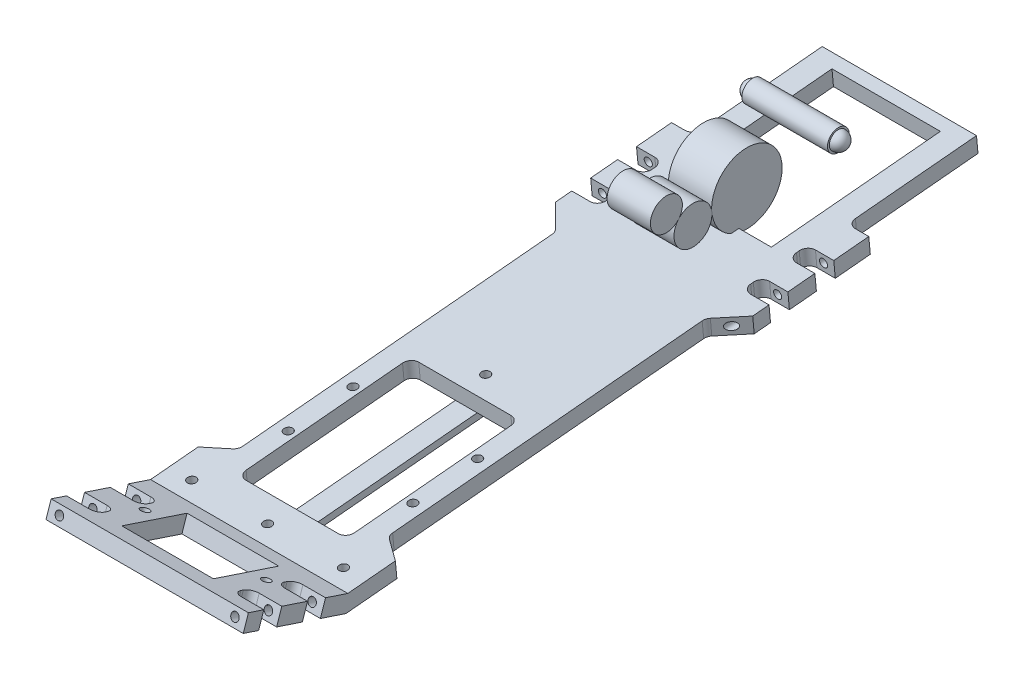
SolidWorks part; units mm, degrees
ref_plane "Front Plane" through (0, 0, 0) normal (0, 0, 1) x (1, 0, 0)
ref_plane "Top Plane" through (0, 0, 0) normal (0, 1, 0) x (1, 0, 0)
ref_plane "Right Plane" through (0, 0, 0) normal (1, 0, 0) x (0, 0, -1)
sketch "Sketch39" plane through (0, 0, 0) normal (1, 0, 0) x (0, 0, -1)
  line L6 (-42.1967, -24.4297) -> (-64.4913, -26.5105)
  line L7 (198.4523, -1.9694) -> (199.1598, -9.55)
  line L8 (-46.4598, -32.3618) -> (199.1598, -9.55)
  line L9 (-46.4598, -32.3618) -> (-111.0949, -11.0354)
  line L10 (-111.0949, -11.0354) -> (-113.4962, -18.2671)
  line L11 (-113.4962, -18.2671) -> (-65.3752, -34.2461)
sketch "Sketch2" plane through (0, 0, 0) normal (1, 0, 0) x (0, 0, -1)
  line L0 (-113.4962, -18.2671) -> (-65.3752, -34.2461)
  line L1 (-65.3752, -34.2461) -> (240.9571, -5.6556)
  line L2 (-64.4913, -26.5105) -> (240.249, 1.9315)
  line L3 (-111.0949, -11.0354) -> (-64.4913, -26.5105)
  line L4 (-113.4962, -18.2671) -> (-111.0949, -11.0354)
  line L6 (240.249, 1.9315) -> (240.9571, -5.6556)
  dimension "D1" = 156.299
  dimension "D2" = 7.62
  dimension "D3" = 7.62
extrude "Frame" add sketch "Sketch2" along normal mid plane 92.456 separate body
sketch "Sketch7" plane through (0, -20.3145, -1.896) normal (0, 0.9957, 0.0929) x (1, 0, 0)
  line L0 (0, -61.0081) -> (0, 34.8348) construction
  line L1 (-25.4, -61.0081) -> (25.4, -61.0081) construction
  line L2 (-21.59, 34.8348) -> (21.59, 34.8348)
  line L4 (55.9608, -51.1889) -> (36.7582, -37.5664)
  line L5 (-55.9608, 133.6584) -> (-55.9608, -51.1889)
  line L6 (-21.59, -46.4124) -> (21.59, -46.4124)
  line L7 (35.1527, -34.4589) -> (35.1527, 111.2721)
  line L8 (36.2686, 113.9662) -> (55.9608, 133.6584)
  line L9 (55.9608, 133.6584) -> (55.9608, -51.1889)
  line L10 (-36.2686, 113.9662) -> (-55.9608, 133.6584)
  line L11 (-35.1527, -34.4589) -> (-35.1527, 111.2721)
  line L12 (-55.9608, -51.1889) -> (-36.7582, -37.5664)
  line L13 (-25.4, 153.6254) -> (25.4, 153.6254)
  line L14 (-25.4, 153.6254) -> (-25.4, 233.1838)
  line L15 (-25.4, 233.1838) -> (25.4, 233.1838)
  line L16 (25.4, 153.6254) -> (25.4, 233.1838)
  line L17 (-25.4, 153.6254) -> (25.4, 233.1838) construction
  line L18 (-25.4, 233.1838) -> (25.4, 153.6254) construction
  line L21 (25.4, 31.0248) -> (25.4, -42.6024)
  line L25 (-25.4, 31.0248) -> (-25.4, -42.6024)
  arc A0 (-36.2686, 113.9662) -> (-35.1527, 111.2721) centre (-38.9627, 111.2721) cw
  arc A1 (35.1527, 111.2721) -> (36.2686, 113.9662) centre (38.9627, 111.2721) cw
  arc A2 (36.7582, -37.5664) -> (35.1527, -34.4589) centre (38.9627, -34.4589) cw
  arc A3 (-35.1527, -34.4589) -> (-36.7582, -37.5664) centre (-38.9627, -34.4589) cw
  arc A4 (-25.4, 31.0248) -> (-21.59, 34.8348) centre (-21.59, 31.0248) cw
  arc A5 (21.59, 34.8348) -> (25.4, 31.0248) centre (21.59, 31.0248) cw
  arc A6 (-25.4, -42.6024) -> (-21.59, -46.4124) centre (-21.59, -42.6024) ccw
  arc A7 (21.59, -46.4124) -> (25.4, -42.6024) centre (21.59, -42.6024) ccw
  circle A11 centre (29.2169, 11.5306) radius 2.032
  circle A13 centre (-29.2169, 11.5306) radius 2.032
  circle A15 centre (-29.2169, -18.9494) radius 2.032
  circle A20 centre (29.2169, -18.9494) radius 2.032
  point P8 (0, -156.8509)
  point P18 (0, -46.4124)
  point P21 (-35.1527, 112.8502)
  point P24 (35.1527, 112.8502)
  point P27 (35.1527, -36.4274)
  point P30 (-35.1527, -36.4274)
  point P33 (-25.4, 34.8348)
  point P36 (25.4, 34.8348)
  point P39 (-25.4, -46.4124)
  point P42 (25.4, -46.4124)
  point P43 (0, 193.4046)
  dimension "D1" = 3.81
extrude "Battery Slot" cut sketch "Sketch7" against normal blind 32.131
sketch "Sketch20" plane through (0, -50.3976, 16.735) normal (0, -0.949, 0.3151) x (1, 0, 0)
  line L0 (54.6923, 94.3364) -> (35.6467, 94.3364)
  line L1 (31.8367, 90.5264) -> (31.8367, 89.2564)
  line L2 (54.6923, 94.3364) -> (54.6923, 63.8564)
  line L3 (35.6467, 85.4464) -> (51.961, 85.4464)
  line L4 (51.961, 85.4464) -> (51.961, 72.7464)
  line L5 (51.961, 72.7464) -> (35.6467, 72.7464)
  line L6 (35.6467, 63.8564) -> (54.6923, 63.8564)
  line L7 (31.8367, 68.9364) -> (31.8367, 67.6664)
  line L8 (0, 135.1129) -> (0, -20.6529) construction
  line L9 (-31.8367, 68.9364) -> (-31.8367, 67.6664)
  line L10 (-35.6467, 63.8564) -> (-54.6923, 63.8564)
  line L11 (-51.961, 72.7464) -> (-35.6467, 72.7464)
  line L12 (-51.961, 85.4464) -> (-51.961, 72.7464)
  line L13 (-35.6467, 85.4464) -> (-51.961, 85.4464)
  line L14 (-54.6923, 94.3364) -> (-54.6923, 63.8564)
  line L15 (-31.8367, 90.5264) -> (-31.8367, 89.2564)
  line L16 (-54.6923, 94.3364) -> (-35.6467, 94.3364)
  line L17 (46.228, 101.9564) -> (-46.228, 101.9564) construction
  arc A0 (35.6467, 72.7464) -> (31.8367, 68.9364) centre (35.6467, 68.9364) ccw
  arc A1 (31.8367, 89.2564) -> (35.6467, 85.4464) centre (35.6467, 89.2564) ccw
  arc A2 (35.6467, 94.3364) -> (31.8367, 90.5264) centre (35.6467, 90.5264) ccw
  arc A3 (31.8367, 67.6664) -> (35.6467, 63.8564) centre (35.6467, 67.6664) ccw
  arc A4 (-31.8367, 67.6664) -> (-35.6467, 63.8564) centre (-35.6467, 67.6664) cw
  arc A5 (-35.6467, 94.3364) -> (-31.8367, 90.5264) centre (-35.6467, 90.5264) cw
  arc A6 (-31.8367, 89.2564) -> (-35.6467, 85.4464) centre (-35.6467, 89.2564) cw
  arc A7 (-35.6467, 72.7464) -> (-31.8367, 68.9364) centre (-35.6467, 68.9364) cw
  point P27 (31.8367, 94.3364)
  point P30 (31.8367, 63.8564)
  dimension "D4" = 3.81
  dimension "D1" = 7.62
  dimension "D2" = 30.48
  dimension "D3" = 12.7
extrude "Extrude25" cut sketch "Sketch20" against normal blind 12.7
sketch "Sketch24" plane through (0, -20.3145, -1.896) normal (0, 0.9957, 0.0929) x (1, 0, 0)
  line L0 (56.4091, 131.6085) -> (56.4091, 162.0885)
  line L1 (46.2491, 175.5574) -> (46.2491, 183.7077) construction
  line L3 (37.6345, 153.1985) -> (52.1938, 153.1985)
  line L4 (52.1938, 153.1985) -> (52.1938, 140.4985)
  line L5 (52.1938, 140.4985) -> (37.6345, 140.4985)
  line L6 (33.8245, 135.4185) -> (33.8245, 136.6885)
  line L7 (33.8245, 157.0085) -> (33.8245, 158.2785)
  line L8 (-37.6345, 131.6085) -> (-56.4091, 131.6085)
  line L9 (-37.6345, 162.0885) -> (-56.4091, 162.0885)
  line L10 (-33.8245, 157.0085) -> (-33.8245, 158.2785)
  line L11 (-33.8245, 135.4185) -> (-33.8245, 136.6885)
  line L12 (0, 232.8671) -> (0, 97.5967) construction
  line L13 (-52.1938, 140.4985) -> (-37.6345, 140.4985)
  line L14 (-52.1938, 153.1985) -> (-52.1938, 140.4985)
  line L15 (37.6345, 162.0885) -> (56.4091, 162.0885)
  line L16 (-37.6345, 153.1985) -> (-52.1938, 153.1985)
  line L17 (-56.4091, 131.6085) -> (-56.4091, 162.0885)
  line L18 (53.9368, 178.5805) -> (39.9686, 178.5805)
  line L19 (36.1586, 182.3905) -> (36.1586, 260.1001)
  line L20 (36.1586, 260.1001) -> (78.0396, 260.1001)
  line L21 (78.0396, 260.1001) -> (53.9368, 178.5805)
  line L23 (-46.2491, 175.5574) -> (-46.2491, 183.7077) construction
  line L24 (37.6345, 131.6085) -> (56.4091, 131.6085)
  line L26 (-78.0396, 260.1001) -> (-53.9368, 178.5805)
  line L27 (-36.1586, 260.1001) -> (-78.0396, 260.1001)
  line L28 (-36.1586, 182.3905) -> (-36.1586, 260.1001)
  line L29 (-53.9368, 178.5805) -> (-39.9686, 178.5805)
  arc A0 (33.8245, 157.0085) -> (37.6345, 153.1985) centre (37.6345, 157.0085) ccw
  arc A1 (33.8245, 158.2785) -> (37.6345, 162.0885) centre (37.6345, 158.2785) cw
  arc A2 (33.8245, 136.6885) -> (37.6345, 140.4985) centre (37.6345, 136.6885) cw
  arc A3 (33.8245, 135.4185) -> (37.6345, 131.6085) centre (37.6345, 135.4185) ccw
  arc A4 (-33.8245, 135.4185) -> (-37.6345, 131.6085) centre (-37.6345, 135.4185) cw
  arc A5 (-33.8245, 136.6885) -> (-37.6345, 140.4985) centre (-37.6345, 136.6885) ccw
  arc A6 (-33.8245, 158.2785) -> (-37.6345, 162.0885) centre (-37.6345, 158.2785) ccw
  arc A7 (-33.8245, 157.0085) -> (-37.6345, 153.1985) centre (-37.6345, 157.0085) cw
  arc A8 (39.9686, 178.5805) -> (36.1586, 182.3905) centre (39.9686, 182.3905) cw
  arc A9 (-39.9686, 178.5805) -> (-36.1586, 182.3905) centre (-39.9686, 182.3905) ccw
  point P11 (33.8245, 162.0885)
  point P23 (33.8245, 140.4985)
  point P35 (33.8245, 131.6085)
  point P42 (-33.8245, 131.6085)
  point P43 (-33.8245, 140.4985)
  point P44 (-33.8245, 162.0885)
  dimension "D5" = 3.81
  dimension "D4" = 3.81
  dimension "D1" = 30.48
  dimension "D2" = 12.7
  dimension "D3" = 8.89
extrude "Low A-Arm Mounting" cut sketch "Sketch24" against normal blind 18.288
sketch "Sketch25" plane through (0, 16.5951, -177.8078) normal (0, 0.0929, -0.9957) x (-1, 0, 0)
  line L0 (-46.228, -24.2128) -> (-27.1638, -24.2128) construction
  line L2 (0, -28.6735) -> (0, 33.6783) construction
  circle A0 centre (-41.0733, -24.2128) radius 1.905
  circle A1 centre (41.0733, -24.2128) radius 1.905
  dimension "D1" = 3.81
extrude "Rear Hinge Holes" cut sketch "Sketch25" against normal blind 72.39
sketch "Sketch26" plane through (0, 0, 0) normal (1, 0, 0) x (0, 0, -1)
  line L0 (133.6432, -15.6714) -> (209.5207, -8.5896) construction
  line L2 (142.0391, -7.2105) -> (132.935, -8.0843) construction
  circle A7 centre (158.6313, 8.3446) radius 21.59 construction
  circle A8 centre (158.6313, 8.3446) radius 16.51
  circle A9 centre (133.3408, 5.9888) radius 8.89
  circle A10 centre (133.3408, 5.9888) radius 13.97 construction
  circle A11 centre (120.9105, 16.6608) radius 7.493
  circle A12 centre (113.1748, 8.7737) radius 18.669
  dimension "D5" = 43.18
  dimension "D6" = 33.02
  dimension "D9" = 17.78
  dimension "D10" = 5.08
  dimension "D11" = 14.986
  dimension "D12" = 37.338
extrude "Extrude18" add sketch "Sketch26" along normal mid plane 20.32 separate body contours A11 | A8 | A9 region at (0, 16.6608, -120.9105)
sketch "Sketch27" plane through (0, 0, 0) normal (1, 0, 0) x (0, 0, -1)
  line L0 (105.7626, -10.6204) -> (103.8445, 9.9304) construction
  line L1 (112.6866, -9.9742) -> (-32.4138, -23.5167) construction
  line L2 (103.8445, 9.9304) -> (195.4808, 18.483) construction
  circle A2 centre (191.5902, 16.3821) radius 5.08
  dimension "D1" = 20.5508
sketch "Sketch32" plane through (0, -50.3976, 16.735) normal (0, -0.949, 0.3151) x (1, 0, 0)
  line L0 (0, 23.7509) -> (0, 127.4595) construction
  line L1 (46.228, 101.9564) -> (-46.228, 101.9564) construction
  line L2 (-21.4758, 93.1386) -> (-21.4758, 60.8931)
  line L3 (-21.4758, 60.8931) -> (21.4758, 60.8931)
  line L4 (-21.4758, 93.1386) -> (21.4758, 93.1386)
  line L5 (21.4758, 93.1386) -> (21.4758, 60.8931)
  circle A0 centre (28.4072, 74.3339) radius 2.032
  circle A1 centre (-28.4072, 74.3339) radius 2.032
  point P11 (0, 93.1386)
  point P15 (0, 60.8931)
  dimension "D2" = 4.064
  dimension "D1" = 27.6225
sketch "Sketch33" plane through (0, -27.9015, -2.6041) normal (0, -0.9957, -0.0929) x (1, 0, 0)
  line L0 (0, -223.696) -> (0, -16.1424) construction
  circle A0 centre (28.4072, -142.6087) radius 2.032
  circle A1 centre (-28.4072, -142.6087) radius 2.032
  circle A6 centre (6.985, -101.7132) radius 1.905
  circle A7 centre (-6.985, -101.7132) radius 1.905
  circle A8 centre (-6.985, -192.4436) radius 1.905
  circle A9 centre (6.985, -192.4436) radius 1.905
  dimension "D1" = 4.064
extrude "Extrude23" [suppressed] cut sketch "Sketch33" against normal blind 47.244
extrude "Extrude24" cut sketch "Sketch32" against normal blind 48.26
sketch "Sketch34" plane through (0, 32.1304, 96.7613) normal (0, 0.3151, 0.949) x (1, 0, 0)
  line L0 (-41.1418, 38.6565) -> (-41.1418, -49.2934) construction
  line L1 (0, 48.2417) -> (0, -27.4221) construction
  line L2 (-46.228, -49.2934) -> (-41.1418, -49.2934) construction
  line L3 (-46.228, -45.4834) -> (-46.228, -53.1034) construction
  circle A0 centre (-41.1418, -49.2934) radius 1.905
  circle A1 centre (41.1418, -49.2934) radius 1.905
  dimension "D1" = 3.81
extrude "Extrude26" cut sketch "Sketch34" against normal blind 45.72
sketch "Sketch38" plane through (0, -20.3145, -1.896) normal (0, 0.9957, 0.0929) x (1, 0, 0)
  line L1 (35.56, -57.9969) -> (0, -57.9969) construction
  circle A0 centre (0, -57.9969) radius 2.032
  circle A1 centre (35.56, -57.9969) radius 2.032
  circle A2 centre (-35.56, -57.9969) radius 2.032
  circle A3 centre (0, 44.6613) radius 2.032
  dimension "D1" = 4.064
  dimension "D2" = 35.56
  dimension "D3" = 35.56
sketch "Sketch36" plane through (0, 0, 0) normal (1, 0, 0) x (0, 0, -1)
  line L0 (-58.53, -18.0678) -> (-55.838, -44.9158) construction
  line L1 (-55.838, -44.9158) -> (-52.047, -44.5357) construction
  line L2 (-52.047, -44.5357) -> (-54.739, -17.6876) construction
  line L3 (-54.739, -17.6876) -> (-58.53, -18.0678) construction
  line L4 (-64.4913, -26.5105) -> (-63.718, -34.223) construction
  line L5 (-46.4598, -32.3618) -> (-47.2072, -24.9082) construction
  line L6 (-41.4886, -32.0168) -> (-42.1967, -24.4297)
  line L7 (211.7309, 10.7495) -> (-145.8776, -22.4632) construction
  line L8 (-64.4913, -26.5105) -> (-74.9362, -23.0422)
  line L9 (-74.9362, -23.0422) -> (-77.3376, -30.2739)
  line L10 (-77.3376, -30.2739) -> (-65.3752, -34.2461)
  line L11 (-65.3752, -34.2461) -> (-41.4886, -32.0168)
  line L12 (-65.3752, -34.2461) -> (-68.8101, -44.5904) construction
  line L13 (-42.1967, -24.4297) -> (-64.4913, -26.5105)
  line L14 (-46.4598, -32.3618) -> (-111.0949, -11.0354)
  line L15 (-111.0949, -11.0354) -> (228.9228, 20.5436) construction
  line L16 (-113.4962, -18.2671) -> (-65.3752, -34.2461)
  line L17 (-46.4598, -32.3618) -> (-65.3752, -34.2461) construction
  line L18 (-64.1047, -30.3668) -> (-46.8335, -28.635) construction
  line L19 (-56.6345, -17.8777) -> (-55.4691, -29.5009) construction
  line L20 (-46.4598, -32.3618) -> (-48.8678, -39.6137) construction
  line L21 (-65.3752, -34.2461) -> (-48.8678, -39.6137) construction
  line L22 (-46.4598, -32.3618) -> (199.1598, -9.55)
  line L23 (-111.0949, -11.0354) -> (-113.4962, -18.2671)
  line L24 (198.4523, -1.9694) -> (199.1598, -9.55)
  line L29 (-42.1967, -24.4297) -> (-64.4913, -26.5105)
  dimension "D2" = 3.81
  dimension "D3" = 17.3578
  dimension "D4" = 17.3578
  dimension "D5" = 19.05
  dimension "D6" = 23.701
  dimension "D7" = 264.0864
  dimension "D8" = 68.0624
  dimension "D9" = 27.2123
  dimension "D1" = 0
extrude "Extrude29" cut sketch "Sketch38" against normal blind 10
sketch "Sketch35" plane through (0, -27.9015, -2.6041) normal (0, -0.9957, -0.0929) x (1, 0, 0)
  line L0 (0, -18.8288) -> (0, 137.2297) construction
  line L1 (5.08, 57.9705) -> (5.08, -44.6613)
  line L2 (0, 66.6492) -> (0, 49.2918) construction
  line L3 (-5.08, -44.6613) -> (-5.0788, 57.8597)
  arc A0 (5.08, 57.9705) -> (-5.0788, 57.8597) centre (0, 57.9705) ccw
  arc A1 (-5.08, -44.6613) -> (5.08, -44.6613) centre (0, -44.6613) ccw
  circle A2 centre (0, -44.6613) radius 2.032
  circle A3 centre (0, 57.9705) radius 2.032
  dimension "D1" = 10.16
  dimension "D2" = 10.16
  dimension "D3" = 4.064
extrude "Extrude30" add sketch "Sketch35" along normal blind 3.175 separate body
extrude "Extrude31" add sketch "Sketch27" along normal mid plane 40.132 separate body
sketch "Sketch40" plane through (-20.066, 0, 0) normal (-1, 0, 0) x (0, 0, 1)
  line L0 (-191.5902, 20.6334) -> (-191.5902, 12.1985) construction
  line L1 (-191.5902, 20.6334) -> (-191.5902, 12.1985)
  arc A1 (-191.5902, 20.6334) -> (-191.5902, 12.1985) centre (-191.5902, 16.4159) cw
revolve "Revolve1" add sketch "Sketch40" angle 360 about L0
mirror "Mirror1" about plane through (0, 0, 0) normal (1, 0, 0) of "Revolve1"
sketch "Sketch41" plane through (0, -20.3145, -1.896) normal (0, 0.9957, 0.0929) x (1, 0, 0)
  line L0 (-35.1527, 44.6613) -> (35.1527, 44.6613) construction
  line L1 (-35.1527, -34.4589) -> (-35.1527, 111.2721) construction
  line L2 (35.1527, 111.2721) -> (35.1527, -34.4589) construction
